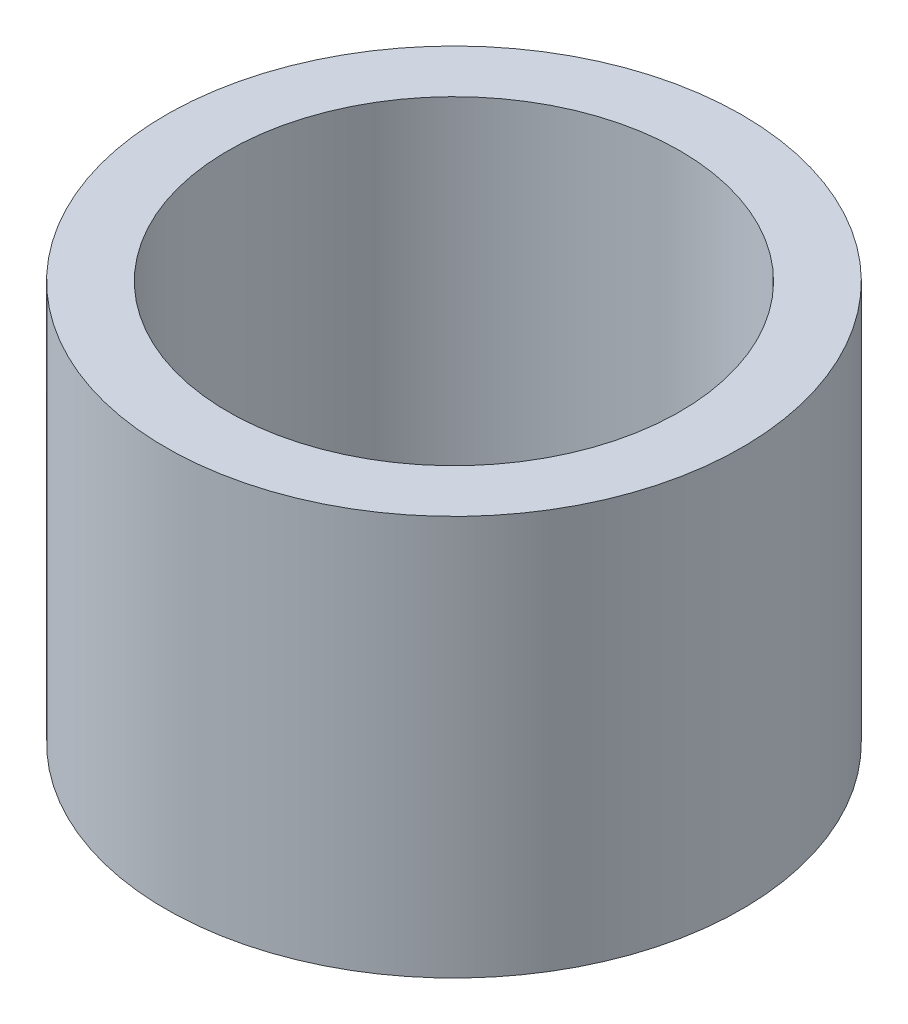
SolidWorks part; units mm, degrees
ref_plane "Front Plane" through (0, 0, 0) normal (0, 0, 1) x (1, 0, 0)
ref_plane "Top Plane" through (0, 0, 0) normal (0, 1, 0) x (1, 0, 0)
ref_plane "Right Plane" through (0, 0, 0) normal (1, 0, 0) x (0, 0, -1)
sketch "Sketch1" plane through (0, 0, 0) normal (0, 1, 0) x (1, 0, 0)
  circle A0 centre (0, 0) radius 20
  dimension "SLEEVE_OD" = 40
extrude "Boss-Extrude1" add sketch "Sketch1" along normal blind 27.7589
sketch "Sketch2" plane through (0, 0, 0) normal (0, 1, 0) x (1, 0, 0)
  circle A0 centre (0, 0) radius 15.6918
  dimension "BORE_D" = 31.3836
extrude "Cut-Extrude1" cut sketch "Sketch2" along normal through all
chamfer "Chamfer1" distance 1.679 angle 60 rebuild error yes
